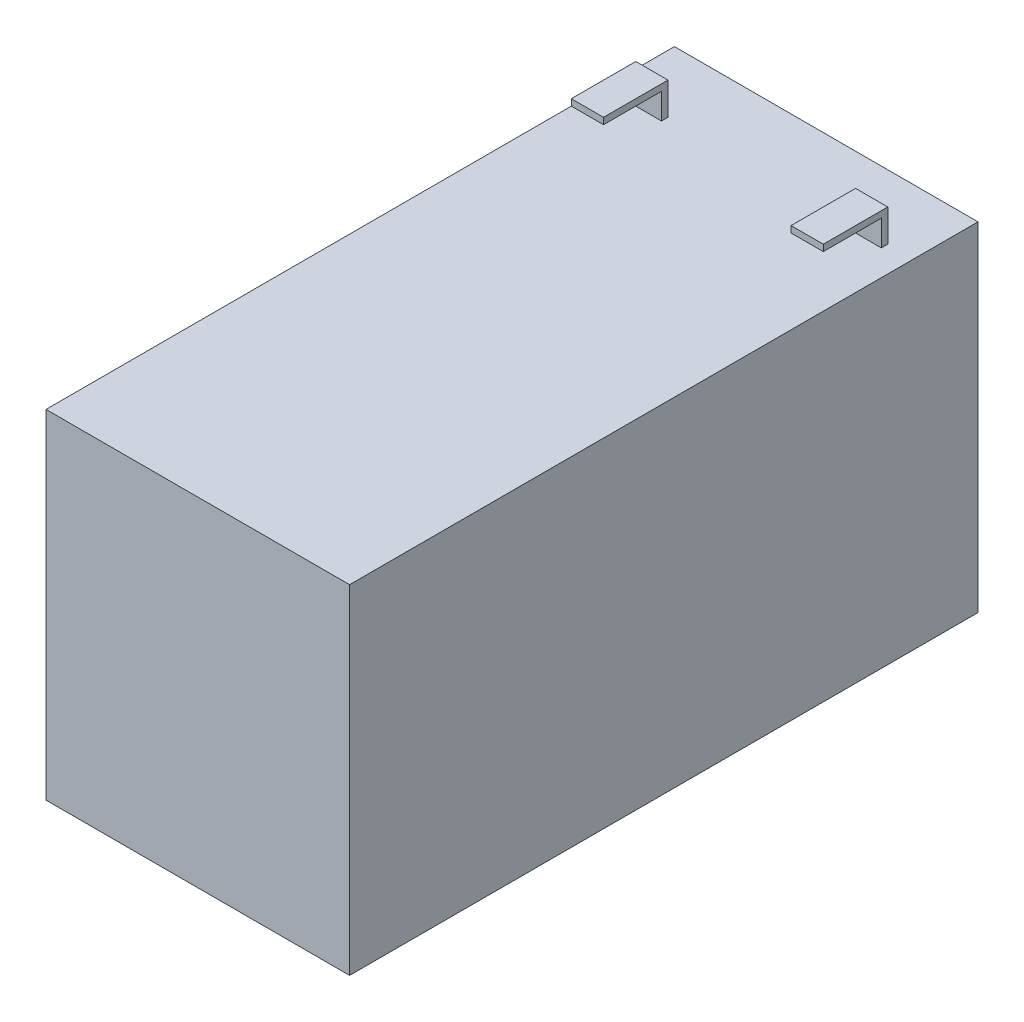
SolidWorks part; units mm, degrees
ref_plane "前视基准面" through (0, 0, 0) normal (0, 0, 1) x (1, 0, 0)
ref_plane "上视基准面" through (0, 0, 0) normal (0, 1, 0) x (1, 0, 0)
ref_plane "右视基准面" through (0, 0, 0) normal (1, 0, 0) x (0, 0, -1)
sketch "草图1" plane through (0, 0, 0) normal (0, 1, 0) x (1, 0, 0)
  line L0 (0, -83.4464) -> (0, 93.8761) construction
  line L1 (-23.55, -48.75) -> (23.55, -48.75)
  line L2 (-23.55, -48.75) -> (-23.55, 48.75)
  line L3 (-23.55, 48.75) -> (23.55, 48.75)
  line L4 (23.55, -48.75) -> (23.55, 48.75)
  line L5 (-72.4379, 0) -> (62.9653, 0) construction
  dimension "D1" = 97.5
  dimension "D2" = 47.1
extrude "拉伸1" add sketch "草图1" along normal blind 52.5
sketch "草图3" plane through (0, 52.5, 0) normal (0, 1, 0) x (-1, 0, 0)
  line L0 (-23.55, -48.75) -> (23.55, -48.75) construction
  line L1 (19.55, -38.75) -> (14.55, -38.75)
  line L2 (19.55, -38.75) -> (19.55, -37.75)
  line L3 (19.55, -37.75) -> (14.55, -37.75)
  line L4 (14.55, -38.75) -> (14.55, -37.75)
  line L5 (23.55, -48.75) -> (23.55, 48.75) construction
  dimension "D1" = 10
  dimension "D2" = 4
  dimension "D3" = 5
  dimension "D4" = 1
ref_plane "基准面1" through (-19.55, 0, 0) normal (-1, 0, 0) x (0, 0, 1)
sketch "草图4" plane through (-19.55, 0, 0) normal (-1, 0, 0) x (0, 0, 1)
  line L0 (-38.75, 52.5) -> (-38.75, 57.5)
  line L1 (-38.75, 57.5) -> (-28.75, 57.5)
  dimension "D1" = 10
  dimension "D2" = 5
sweep "扫描1" add profiles "草图3" path "草图4"
ref_plane "基准面2" through (0, 0, 0) normal (-1, 0, 0) x (0, 0, 1)
mirror "镜向2" about plane through (0, 0, 0) normal (-1, 0, 0) of "扫描1"
